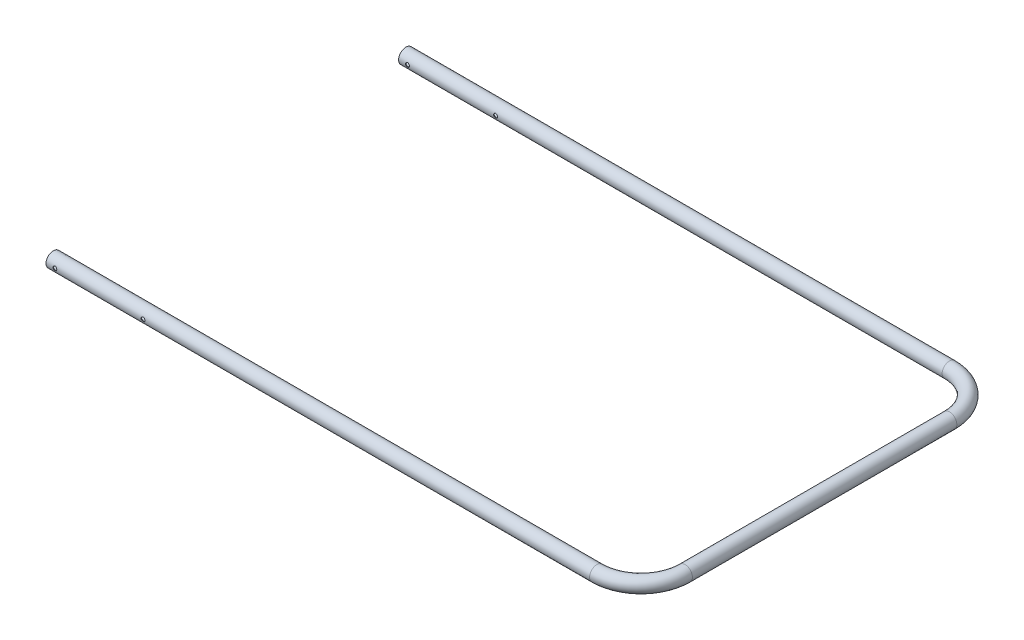
SolidWorks part; units mm, degrees
ref_plane "Front Plane" through (0, 0, 0) normal (0, 0, 1) x (1, 0, 0)
ref_plane "Top Plane" through (0, 0, 0) normal (0, 1, 0) x (1, 0, 0)
ref_plane "Right Plane" through (0, 0, 0) normal (1, 0, 0) x (0, 0, -1)
sketch "Sketch1" plane through (0, 0, 0) normal (0, 1, 0) x (1, 0, 0)
  line L0 (0, 0) -> (-760.5369, 0) construction
  line L1 (0, -228.6) -> (0, 228.6)
  line L2 (-76.2, 304.8) -> (-1016, 304.8)
  line L3 (-76.2, -304.8) -> (-1016, -304.8)
  arc A0 (0, -228.6) -> (-76.2, -304.8) centre (-76.2, -228.6) cw
  arc A1 (0, 228.6) -> (-76.2, 304.8) centre (-76.2, 228.6) ccw
  dimension "D3" = 76.2
  dimension "D1" = 609.6
  dimension "D2" = 1016
ref_plane "Plane1" through (-1016, 0, 0) normal (1, 0, 0) x (0, 0, -1)
sketch "Sketch2" plane through (-1016, 0, 0) normal (1, 0, 0) x (0, 0, -1)
  circle A0 centre (304.8, 0) radius 12.7
  dimension "D1" = 25.4
sweep "Sweep-Thin1" add profiles "Sketch2" path "Sketch1" parameters "D1"=1
sketch "Sketch3" plane through (0, 0, 0) normal (0, 0, 1) x (1, 0, 0)
  line L0 (-1016, -13.97) -> (-1016, 13.97) construction
  circle A0 centre (-1000.76, 0) radius 3.3782
  dimension "D1" = 6.7564
  dimension "D2" = 15.24
extrude "Cut-Extrude1" cut sketch "Sketch3" against normal through all both and the other way through all
sketch "Sketch4" plane through (0, 0, 0) normal (0, 0, 1) x (1, 0, 0)
  circle A0 centre (-848.36, 0) radius 3.3782
  circle A1 centre (-1000.76, 0) radius 3.3782 construction
  dimension "D1" = 152.4
  dimension "D2" = 6.7564
extrude "Cut-Extrude2" cut sketch "Sketch4" against normal through all both and the other way through all
ref_axis "Axis1" through (-76.2, 0, 304.8) along (-1, 0, 0)
ref_axis "Axis2" through (-1016, 0, -304.8) along (1, 0, 0)
sketch "Sketch5" plane through (0, 0, 0) normal (0, 1, 0) x (1, 0, 0)
  line L0 (-76.2, 304.8) -> (-1016, 304.8) construction
  line L1 (0, -228.6) -> (0, 228.6) construction
  line L2 (-76.2, -304.8) -> (-1016, -304.8) construction
  line L3 (-76.2, 304.8) -> (-1016, 304.8)
  line L4 (0, -228.6) -> (0, 228.6)
  line L5 (-76.2, -304.8) -> (-1016, -304.8)
  arc A0 (0, 228.6) -> (-76.2, 304.8) centre (-76.2, 228.6) ccw construction
  arc A1 (-76.2, -304.8) -> (0, -228.6) centre (-76.2, -228.6) ccw construction
  arc A2 (0, 228.6) -> (-76.2, 304.8) centre (-76.2, 228.6) ccw
  arc A3 (-76.2, -304.8) -> (0, -228.6) centre (-76.2, -228.6) ccw
